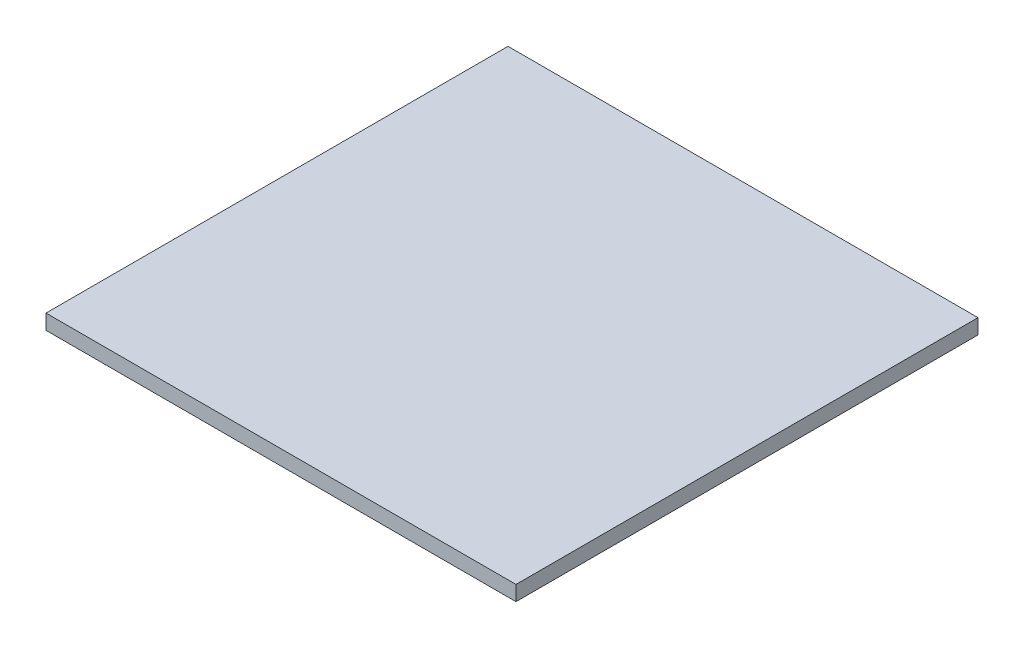
SolidWorks part; units mm, degrees
ref_plane "Front Plane" through (0, 0, 0) normal (0, 0, 1) x (1, 0, 0)
ref_plane "Top Plane" through (0, 0, 0) normal (0, 1, 0) x (1, 0, 0)
ref_plane "Right Plane" through (0, 0, 0) normal (1, 0, 0) x (0, 0, -1)
sketch "Sketch1" plane through (0, 0, 0) normal (0, 1, 0) x (1, 0, 0)
  line L1 (-44.2815, 20.698) -> (56.2185, 20.698)
  line L2 (-44.2815, 20.698) -> (-44.2815, -78.102)
  line L3 (-44.2815, -78.102) -> (56.2185, -78.102)
  line L4 (56.2185, 20.698) -> (56.2185, -78.102)
  dimension "D1" = 100.5
  dimension "D2" = 98.8
extrude "Boss-Extrude1" add sketch "Sketch1" along normal blind 3.2
equation "\"Fit\"= 1"
equation "\"cover width\"= 98.8"
equation "\"bottom 1 length\"= 100.5"
equation "\"thinner acrylic\"= 3.2"
equation "\"D1@Sketch1\"=\"bottom 1 length\""
equation "\"D2@Sketch1\"=\"cover width\""
equation "\"D1@Boss-Extrude1\"=\"thinner acrylic\""
